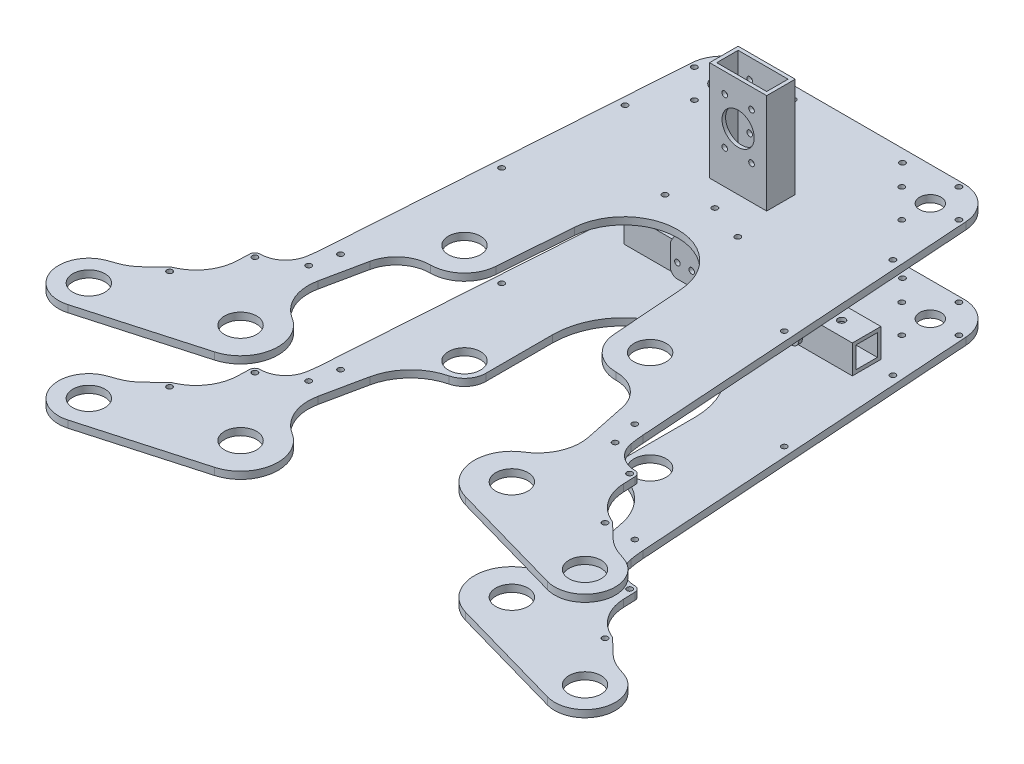
SolidWorks part; units mm, degrees
ref_plane "Alzado" through (0, 0, 0) normal (0, 0, 1) x (1, 0, 0)
ref_plane "Planta" through (0, 0, 0) normal (0, 1, 0) x (1, 0, 0)
ref_plane "Vista lateral" through (0, 0, 0) normal (1, 0, 0) x (0, 0, -1)
sketch "llantas" plane through (0, 0, 0) normal (0, 1, 0) x (1, 0, 0)
  line L0 (0, 221.5734) -> (0, 0) construction
  line L1 (-215.9, 0) -> (0, 0) construction
  circle A0 centre (-93.6625, 101.6) radius 50.8
  circle A1 centre (-215.9, 0) radius 38.1
  circle A2 centre (215.9, 0) radius 38.1
  circle A3 centre (93.6625, 101.6) radius 50.8
  dimension "D1" = 101.6
  dimension "D2" = 42.8625
  dimension "D3" = 177.8
  dimension "D4" = 76.2
  dimension "D5" = 101.6
sketch "cono" plane through (0, 0, 0) normal (1, 0, 0) x (0, 0, -1)
  line L0 (-76.2, 23.114) -> (-22.987, 324.358)
  line L1 (-22.987, 324.358) -> (22.987, 324.358)
  line L2 (0, 324.358) -> (0, 23.114) construction
  line L3 (76.2, 23.114) -> (-76.2, 23.114) construction
  line L4 (-76.2, 23.114) -> (-106.426, 23.114)
  line L5 (-106.426, 23.114) -> (-106.426, 0)
  line L6 (-106.426, 0) -> (106.426, 0)
  line L7 (0, 0) -> (0, 23.114)
  line L8 (-76.2, 23.114) -> (76.2, 23.114)
  line L9 (-80.283, 0) -> (80.283, 0)
  line L10 (221.5734, 0) -> (0, 0) construction
  line L11 (106.426, 23.114) -> (106.426, 0)
  line L12 (76.2, 23.114) -> (106.426, 23.114)
  line L13 (76.2, 23.114) -> (22.987, 324.358)
  line L14 (0, 220.8278) -> (41.275, 220.8278) construction
  dimension "D1" = 324.358
  dimension "D2" = 23.114
  dimension "D3" = 22.987
  dimension "D4" = 152.4
  dimension "D5" = 212.852
  dimension "D6" = 41.275
  dimension "D7" = 220.8278
sketch "Croquis4" plane through (0, 0, 0) normal (0, 1, 0) x (1, 0, 0)
  line L11 (0, 293.4478) -> (0, -300.8756) construction
  circle A36 centre (0, 179.087) radius 32.258
  dimension "D4" = 64.516
ref_plane "Plano1" through (0, 184.15, 0) normal (0, 1, 0) x (1, 0, 0)
sketch "Croquis11" plane through (0, 184.15, 0) normal (0, 1, 0) x (1, 0, 0)
  line L0 (0, -106.426) -> (0, 106.426) construction
  line L1 (-101.7784, 180.6897) -> (-111.1757, -58.1023) construction
  line L2 (0, 0) -> (0, -47.7539) construction
  line L3 (-82.7561, 181.459) -> (-54.1087, -55.7947) construction
  line L4 (-102.0644, -224.6803) -> (-63.9644, -63.6256) construction
  line L5 (-139.2356, -215.8869) -> (-101.1356, -54.8321) construction
  line L6 (0, 0) -> (-82.55, -59.2289) construction
  line L7 (0, 0) -> (0, -106.426) construction
  line L14 (-126.947, -202.253) -> (-226.9506, -237.178) construction
  line L15 (-114.353, -238.3143) -> (-214.3566, -273.2393) construction
  line L16 (0, 293.4478) -> (0, -300.8756) construction
  line L17 (-220.6536, -283.7836) -> (-120.65, -283.7836) construction
  circle A0 centre (0, 0) radius 47.7539 construction
  circle A1 centre (-82.55, -59.2289) radius 50.8
  circle A2 centre (-92.2365, 180.3142) radius 30
  arc A3 (-82.7561, 181.459) -> (-101.7784, 180.6897) centre (-92.2365, 180.3142) ccw construction
  arc A4 (-111.1757, -58.1023) -> (-54.1087, -55.7947) centre (-82.55, -59.2289) ccw construction
  arc A6 (-139.2356, -215.8869) -> (-102.0644, -224.6803) centre (-120.65, -220.2836) ccw construction
  arc A7 (-63.9644, -63.6256) -> (-101.1356, -54.8321) centre (-82.55, -59.2289) ccw construction
  circle A12 centre (-120.65, -220.2836) radius 50.8
  circle A13 centre (-220.6536, -255.2086) radius 28.575
  arc A14 (-226.9506, -237.178) -> (-214.3566, -273.2393) centre (-220.6536, -255.2086) ccw construction
  arc A15 (-114.353, -238.3143) -> (-139.2356, -215.8869) centre (-120.65, -220.2836) ccw construction
  dimension "D1" = 101.6
  dimension "D4" = 60
  dimension "D5" = 19.0986
  dimension "D6" = 57.2958
  dimension "D10" = 38.1972
  dimension "D17" = 101.6
  dimension "D13" = 57.15
  dimension "D14" = 38.1972
  dimension "D2" = 101.6
  dimension "D3" = 165.1
  dimension "D8" = 69.85
  dimension "D9" = 12.7
  dimension "D12" = 239.5431
sketch "Croquis40" plane through (0, 184.15, 0) normal (0, 1, 0) x (1, 0, 0)
  line L0 (-117.475, -110.0289) -> (117.475, -110.0289) construction
  line L1 (-117.475, -110.0289) -> (-117.475, -344.9789) construction
  line L2 (117.475, -110.0289) -> (117.475, -344.9789) construction
  line L3 (-117.475, -344.9789) -> (117.475, -344.9789) construction
  line L4 (0, 0) -> (0, -110.0289)
  circle A1 centre (-82.55, -59.2289) radius 50.8 construction
  dimension "D1" = 234.95
ref_plane "Plano2" through (0, 95.25, 0) normal (0, 1, 0) x (1, 0, 0)
sketch "Croquis12" plane through (0, 95.25, 0) normal (0, 1, 0) x (1, 0, 0)
  line L0 (0, 0) -> (0, -63.4576) construction
  circle A0 centre (0, 0) radius 63.4576 construction
  circle A1 centre (-82.55, -59.2289) radius 50.8
  circle A2 centre (-82.55, -59.2289) radius 50.8 construction
sketch "Croquis42" plane through (0, 184.15, 0) normal (0, 1, 0) x (1, 0, 0)
  line L10 (142.9479, -125.9298) -> (122.1686, 182.3319)
  line L11 (-47.6217, 3.5515) -> (-52.471, -61.4721)
  line L12 (-112.3836, -113.6275) -> (-120.3575, -151.7275)
  line L13 (-120.65, -220.2836) -> (-220.6536, -255.2086) construction
  line L14 (-111.5648, -252.3593) -> (-213.299, -281.1746)
  line L15 (0, 226.6032) -> (0, -226.6032) construction
  line L17 (229.5516, -229.7302) -> (219.3033, -226.1511)
  line L18 (-229.5516, -229.7302) -> (-219.3033, -226.1511)
  line L19 (-142.9479, -125.9298) -> (-122.1686, 182.3319)
  line L20 (-126.947, -202.253) -> (-226.9506, -237.178) construction
  line L21 (-92.2365, 210.3142) -> (92.2365, 210.3142)
  line L22 (111.5648, -252.3593) -> (213.299, -281.1746)
  line L23 (112.3836, -113.6275) -> (120.3575, -151.7275)
  line L24 (47.6217, 3.5515) -> (52.471, -61.4721)
  circle A11 centre (-220.6536, -255.2086) radius 14.2875
  circle A17 centre (-120.65, -220.2836) radius 14.2875
  circle A18 centre (-82.55, -59.2289) radius 14.2875
  arc A20 (47.6217, 3.5515) -> (-47.6217, 3.5515) centre (0, 0) ccw
  circle A21 centre (92.2365, 180.3142) radius 25.4 construction
  circle A22 centre (0, 0) radius 47.7539 construction
  arc A23 (-82.55, -89.3914) -> (-52.471, -61.4721) centre (-82.55, -59.2289) ccw
  arc A24 (-82.55, -89.3914) -> (-112.3836, -113.6275) centre (-82.55, -119.8714) ccw
  arc A25 (-111.5648, -252.3593) -> (-103.1106, -191.933) centre (-120.65, -220.2836) ccw
  arc A26 (-120.3575, -151.7275) -> (-103.1106, -191.933) centre (-83.0655, -159.5323) ccw
  arc A28 (-229.5516, -229.7302) -> (-213.299, -281.1746) centre (-220.6536, -255.2086) ccw
  circle A29 centre (120.65, -220.2836) radius 33.3375 construction
  circle A30 centre (117.6365, 180.3142) radius 2.4892
  circle A31 centre (-92.2365, 180.3142) radius 30 construction
  arc A32 (-92.2365, 210.3142) -> (-122.1686, 182.3319) centre (-92.2365, 180.3142) ccw
  circle A33 centre (-120.65, -220.2836) radius 33.3375 construction
  circle A34 centre (-92.2365, 180.3142) radius 25.4 construction
  circle A35 centre (-92.2365, 205.7142) radius 2.4892
  circle A36 centre (-66.8365, 180.3142) radius 2.4892
  circle A37 centre (-92.2365, 154.9142) radius 2.4892
  circle A38 centre (-117.6365, 180.3142) radius 2.4892
  circle A39 centre (92.2365, 154.9142) radius 2.4892
  circle A40 centre (66.8365, 180.3142) radius 2.4892
  circle A41 centre (92.2365, 205.7142) radius 2.4892
  arc A42 (92.2365, 210.3142) -> (122.1686, 182.3319) centre (92.2365, 180.3142) cw
  arc A43 (229.5516, -229.7302) -> (213.299, -281.1746) centre (220.6536, -255.2086) cw
  arc A44 (120.3575, -151.7275) -> (103.1106, -191.933) centre (83.0655, -159.5323) cw
  arc A45 (111.5648, -252.3593) -> (103.1106, -191.933) centre (120.65, -220.2836) cw
  arc A46 (82.55, -89.3914) -> (112.3836, -113.6275) centre (82.55, -119.8714) cw
  arc A47 (82.55, -89.3914) -> (52.471, -61.4721) centre (82.55, -59.2289) cw
  circle A48 centre (82.55, -59.2289) radius 14.2875
  circle A49 centre (120.65, -220.2836) radius 14.2875
  circle A50 centre (220.6536, -255.2086) radius 14.2875
  arc A52 (142.9479, -125.9298) -> (219.3033, -226.1511) centre (256.9891, -118.2425) ccw
  arc A53 (-219.3033, -226.1511) -> (-142.9479, -125.9298) centre (-256.9891, -118.2425) ccw
  circle A54 centre (-92.2365, 180.3142) radius 9.5631
  circle A55 centre (92.2365, 180.3142) radius 9.5631
  point P18 (-170.6518, -237.7461)
  point P52 (-92.2365, 180.3142)
  point P66 (148.0256, -201.2583)
  point P83 (0, 210.3142)
  point P85 (92.2365, 180.3142)
  point P86 (170.6518, -237.7461)
  point P90 (-148.0256, -201.2583)
  dimension "D1" = 28.575
  dimension "D2" = 19.05
  dimension "D3" = 12.7
  dimension "D4" = 15.875
  dimension "D5" = 38.1
  dimension "D7" = 30.48
  dimension "D8" = 50.8
  dimension "D9" = 4.9784
  dimension "D11" = 114.3
  dimension "D12" = 19.1262
  dimension "D6" = 38.1
  dimension "D10" = 4
extrude "4400-23-P-0501" add sketch "Croquis42" along normal blind 6.35
sketch "Croquis44" plane through (0, 95.25, 0) normal (0, 1, 0) x (1, 0, 0)
  line L0 (92.2365, 210.3142) -> (-92.2365, 210.3142) construction
  line L1 (-122.1686, 182.3319) -> (-142.9479, -125.9298) construction
  line L2 (92.2365, 210.3142) -> (-92.2365, 210.3142)
  line L3 (-122.1686, 182.3319) -> (-142.9479, -125.9298)
  line L4 (142.9479, -125.9298) -> (122.1686, 182.3319) construction
  line L5 (229.5516, -229.7302) -> (219.3033, -226.1511) construction
  line L6 (111.5648, -252.3593) -> (213.299, -281.1746) construction
  line L7 (112.3836, -113.6275) -> (120.3575, -151.7275) construction
  line L10 (-120.3575, -151.7275) -> (-112.3836, -113.6275) construction
  line L11 (-213.299, -281.1746) -> (-111.5648, -252.3593) construction
  line L12 (-219.3033, -226.1511) -> (-229.5516, -229.7302) construction
  line L13 (142.9479, -125.9298) -> (122.1686, 182.3319)
  line L14 (229.5516, -229.7302) -> (219.3033, -226.1511)
  line L15 (111.5648, -252.3593) -> (213.299, -281.1746)
  line L16 (112.3836, -113.6275) -> (120.3575, -151.7275)
  line L19 (-120.3575, -151.7275) -> (-112.3836, -113.6275)
  line L20 (-213.299, -281.1746) -> (-111.5648, -252.3593)
  line L21 (-219.3033, -226.1511) -> (-229.5516, -229.7302)
  line L22 (-63.4576, -59.2289) -> (-63.4576, 0)
  line L23 (63.4576, -59.2289) -> (63.4576, 0)
  line L24 (0, 0) -> (0, -147.841) construction
  arc A0 (-219.3033, -226.1511) -> (-142.9479, -125.9298) centre (-256.9891, -118.2425) ccw construction
  arc A1 (-92.2365, 210.3142) -> (-122.1686, 182.3319) centre (-92.2365, 180.3142) ccw construction
  arc A2 (-219.3033, -226.1511) -> (-142.9479, -125.9298) centre (-256.9891, -118.2425) ccw
  arc A3 (-92.2365, 210.3142) -> (-122.1686, 182.3319) centre (-92.2365, 180.3142) ccw
  arc A4 (122.1686, 182.3319) -> (92.2365, 210.3142) centre (92.2365, 180.3142) ccw construction
  arc A5 (142.9479, -125.9298) -> (219.3033, -226.1511) centre (256.9891, -118.2425) ccw construction
  arc A6 (213.299, -281.1746) -> (229.5516, -229.7302) centre (220.6536, -255.2086) ccw construction
  arc A7 (103.1106, -191.933) -> (111.5648, -252.3593) centre (120.65, -220.2836) ccw construction
  arc A8 (103.1106, -191.933) -> (120.3575, -151.7275) centre (83.0655, -159.5323) ccw construction
  arc A14 (-120.3575, -151.7275) -> (-103.1106, -191.933) centre (-83.0655, -159.5323) ccw construction
  arc A15 (-111.5648, -252.3593) -> (-103.1106, -191.933) centre (-120.65, -220.2836) ccw construction
  arc A16 (-229.5516, -229.7302) -> (-213.299, -281.1746) centre (-220.6536, -255.2086) ccw construction
  arc A17 (122.1686, 182.3319) -> (92.2365, 210.3142) centre (92.2365, 180.3142) ccw
  arc A18 (142.9479, -125.9298) -> (219.3033, -226.1511) centre (256.9891, -118.2425) ccw
  arc A19 (213.299, -281.1746) -> (229.5516, -229.7302) centre (220.6536, -255.2086) ccw
  arc A20 (103.1106, -191.933) -> (111.5648, -252.3593) centre (120.65, -220.2836) ccw
  arc A21 (103.1106, -191.933) -> (120.3575, -151.7275) centre (83.0655, -159.5323) ccw
  arc A27 (-120.3575, -151.7275) -> (-103.1106, -191.933) centre (-83.0655, -159.5323) ccw
  arc A28 (-111.5648, -252.3593) -> (-103.1106, -191.933) centre (-120.65, -220.2836) ccw
  arc A29 (-229.5516, -229.7302) -> (-213.299, -281.1746) centre (-220.6536, -255.2086) ccw
  circle A30 centre (92.2365, 180.3142) radius 9.5631 construction
  circle A31 centre (92.2365, 154.9142) radius 2.4892 construction
  circle A32 centre (117.6365, 180.3142) radius 2.4892 construction
  circle A33 centre (92.2365, 205.7142) radius 2.4892 construction
  circle A34 centre (66.8365, 180.3142) radius 2.4892 construction
  circle A35 centre (-92.2365, 180.3142) radius 9.5631 construction
  circle A36 centre (-66.8365, 180.3142) radius 2.4892 construction
  circle A37 centre (-92.2365, 205.7142) radius 2.4892 construction
  circle A38 centre (-117.6365, 180.3142) radius 2.4892 construction
  circle A39 centre (-92.2365, 154.9142) radius 2.4892 construction
  circle A40 centre (220.6536, -255.2086) radius 14.2875 construction
  circle A41 centre (120.65, -220.2836) radius 14.2875 construction
  circle A42 centre (82.55, -59.2289) radius 14.2875 construction
  circle A43 centre (-82.55, -59.2289) radius 14.2875 construction
  circle A44 centre (-120.65, -220.2836) radius 14.2875 construction
  circle A45 centre (-220.6536, -255.2086) radius 14.2875 construction
  circle A46 centre (92.2365, 180.3142) radius 9.5631
  circle A47 centre (92.2365, 154.9142) radius 2.4892
  circle A48 centre (117.6365, 180.3142) radius 2.4892
  circle A49 centre (92.2365, 205.7142) radius 2.4892
  circle A50 centre (66.8365, 180.3142) radius 2.4892
  circle A51 centre (-92.2365, 180.3142) radius 9.5631
  circle A52 centre (-66.8365, 180.3142) radius 2.4892
  circle A53 centre (-92.2365, 205.7142) radius 2.4892
  circle A54 centre (-117.6365, 180.3142) radius 2.4892
  circle A55 centre (-92.2365, 154.9142) radius 2.4892
  circle A56 centre (220.6536, -255.2086) radius 14.2875
  circle A57 centre (120.65, -220.2836) radius 14.2875
  circle A58 centre (82.55, -59.2289) radius 14.2875
  circle A59 centre (-82.55, -59.2289) radius 14.2875
  circle A60 centre (-120.65, -220.2836) radius 14.2875
  circle A61 centre (-220.6536, -255.2086) radius 14.2875
  arc A62 (63.4576, 0) -> (-63.4576, 0) centre (0, 0) ccw
  arc A64 (-63.4576, -59.2289) -> (-77.9, -77.7463) centre (-82.55, -59.2289) cw
  arc A65 (-112.3836, -113.6275) -> (-77.9, -77.7463) centre (-66.477, -123.2353) cw
  circle A66 centre (0, 0) radius 63.4576 construction
  arc A67 (112.3836, -113.6275) -> (77.9, -77.7463) centre (66.477, -123.2353) ccw
  arc A68 (63.4576, -59.2289) -> (77.9, -77.7463) centre (82.55, -59.2289) ccw
extrude "4400-23-P-0502" add sketch "Croquis44" along normal blind 6.35
sketch "Croquis45" plane through (0, 95.25, 0) normal (0, -1, 0) x (1, 0, 0)
  line L7 (-126.947, 202.253) -> (-226.9506, 237.178) construction
  circle A0 centre (-189.6273, 213.7178) radius 4.7625 construction
  circle A1 centre (-189.6273, 213.7178) radius 2.4892
  circle A6 centre (-220.6536, 255.2086) radius 38.1
  circle A7 centre (-220.6536, 255.2086) radius 38.1 construction
  circle A9 centre (-120.65, 220.2836) radius 63.5
  circle A10 centre (-120.65, 220.2836) radius 63.5 construction
  dimension "D1" = 9.525
  dimension "D2" = 4.9784
  dimension "D5" = 5.08
  dimension "D3" = 9.525
  dimension "D4" = 12.7
sketch "Croquis46" plane through (0, 190.5, 0) normal (0, 1, 0) x (1, 0, 0)
  line L0 (-184.6841, -242.6467) -> (-180.5992, -241.2201) construction
  line L1 (-126.947, -202.253) -> (-226.9506, -237.178) construction
  line L2 (-220.6536, -255.2086) -> (-120.65, -220.2836) construction
  line L3 (-182.6417, -241.9334) -> (-193.6494, -210.4142) construction
  line L4 (-166.6601, -156.7836) -> (-120.65, -156.7836) construction
  line L5 (-215.2247, -224.639) -> (-196.9587, -206.9893)
  line L6 (-172.6356, -195.3721) -> (-195.6603, -206.0971)
  line L7 (-172.6356, -195.3721) -> (-171.4196, -161.3759)
  line L8 (0, 0) -> (0, -195.4432) construction
  line L9 (166.6601, -156.7836) -> (120.65, -156.7836) construction
  line L10 (182.6417, -241.9334) -> (193.6494, -210.4142) construction
  line L11 (220.6536, -255.2086) -> (120.65, -220.2836) construction
  line L12 (184.6841, -242.6467) -> (180.5992, -241.2201) construction
  line L13 (172.6356, -195.3721) -> (171.4196, -161.3759)
  line L14 (172.6356, -195.3721) -> (195.6603, -206.0971)
  line L15 (215.2247, -224.639) -> (196.9587, -206.9893)
  circle A0 centre (-220.6536, -255.2086) radius 38.1 construction
  circle A1 centre (-193.6494, -210.4142) radius 4.7625 construction
  circle A2 centre (-193.6494, -210.4142) radius 2.4892
  circle A3 centre (-166.6601, -161.5461) radius 4.7625 construction
  circle A4 centre (-166.6601, -161.5461) radius 2.4892
  arc A5 (-219.3033, -226.1511) -> (-142.9479, -125.9298) centre (-256.9891, -118.2425) ccw construction
  circle A6 centre (-120.65, -220.2836) radius 63.5 construction
  arc A7 (-196.9587, -206.9893) -> (-195.6603, -206.0971) centre (-193.6494, -210.4142) cw
  arc A8 (-171.4196, -161.3759) -> (-166.6601, -156.7836) centre (-166.6601, -161.5461) cw
  arc A9 (-166.6601, -156.7836) -> (-144.4349, -138.1433) centre (-166.6601, -134.2137) ccw
  arc A10 (-215.2247, -224.639) -> (-144.4349, -138.1433) centre (-256.9891, -118.2425) ccw
  circle A11 centre (166.6601, -161.5461) radius 4.7625 construction
  circle A12 centre (193.6494, -210.4142) radius 4.7625 construction
  arc A13 (215.2247, -224.639) -> (144.4349, -138.1433) centre (256.9891, -118.2425) cw
  arc A14 (166.6601, -156.7836) -> (144.4349, -138.1433) centre (166.6601, -134.2137) cw
  arc A15 (171.4196, -161.3759) -> (166.6601, -156.7836) centre (166.6601, -161.5461) ccw
  arc A16 (196.9587, -206.9893) -> (195.6603, -206.0971) centre (193.6494, -210.4142) ccw
  circle A17 centre (166.6601, -161.5461) radius 2.4892
  circle A18 centre (193.6494, -210.4142) radius 2.4892
  point P20 (-182.6417, -241.9334)
  arc M29 (219.3033, -226.1511) -> (142.9479, -125.9298) centre (256.9891, -118.2425) cw
  arc M35 (-142.9479, -125.9298) -> (-219.3033, -226.1511) centre (-256.9891, -118.2425) cw
  dimension "D1" = 4.9784
  dimension "D2" = 9.525
  dimension "D4" = 6.35
  dimension "D3" = 9.525
  dimension "D5" = 25.4
extrude "Saliente-Extruir2" add sketch "Croquis46" against normal up to surface (6.35 mm away) contours A9 A8 L7 A4 M35 | A7 L5 A2 L6 M35 | L13 A15 A14 A17 M29 | A18 L15 A16 L14 M29 region at (-162.2772, 190.5, 168.9624) region at (-205.7326, 190.5, 216.1858) region at (162.2772, 190.5, 168.9624) region at (183.9298, 190.5, 201.203) up to face at (0, 184.15, 101.9028)
fillet "Redondeo1" radius 38.1 2 edges at (-215.2247, 187.325, 224.639) (-172.6356, 187.325, 195.3721)
extrude "Saliente-Extruir3" add sketch "Croquis46<3>" against normal up to surface (95.25 mm away) from surface contours A9 A8 L7 A4 M35 | A7 L5 A2 L6 M35 | L13 A15 A14 A17 M29 | A18 L15 A16 L14 M29 region at (-162.2772, 190.5, 168.9624) region at (-205.7326, 190.5, 216.1858) region at (162.2772, 190.5, 168.9624) region at (183.9298, 190.5, 201.203) up to face at (0, 95.25, 100.1304) starting at face at (-120.65, 101.6, 234.5711)
sketch "Croquis46<3>" plane through (0, 190.5, 0) normal (0, 1, 0) x (1, 0, 0) same geometry as "Croquis46"
fillet "Redondeo2" radius 38.1 2 edges at (-215.2247, 98.425, 224.639) (-172.6356, 98.425, 195.3721)
fillet "Redondeo3" radius 38.1 2 edges at (215.2247, 187.325, 224.639) (172.6356, 187.325, 195.3721)
fillet "Redondeo4" radius 38.1 2 edges at (215.2247, 98.425, 224.639) (172.6356, 98.425, 195.3721)
sketch "Croquis47" plane through (0, 190.5, 0) normal (0, 1, 0) x (1, 0, 0)
  line L0 (-139.2356, -215.8869) -> (-101.1356, -54.8321) construction
  line L4 (0, 0) -> (0, -211.1114) construction
  line L9 (-101.7784, 180.6897) -> (-111.1757, -58.1023) construction
  line L12 (92.2365, 210.3142) -> (-92.2365, 210.3142) construction
  line L14 (-82.7561, 181.459) -> (-54.1087, -55.7947) construction
  circle A0 centre (-136.2788, -144.0836) radius 4.7625 construction
  circle A1 centre (-136.2788, -144.0836) radius 2.4892
  circle A2 centre (-130.8514, -121.1414) radius 4.7625 construction
  circle A3 centre (-130.8514, -121.1414) radius 2.4892
  circle A5 centre (-120.65, -220.2836) radius 63.5 construction
  circle A7 centre (-82.55, -59.2289) radius 50.8 construction
  circle A8 centre (130.8514, -121.1414) radius 2.4892
  circle A9 centre (130.8514, -121.1414) radius 4.7625 construction
  circle A10 centre (136.2788, -144.0836) radius 2.4892
  circle A11 centre (136.2788, -144.0836) radius 4.7625 construction
  circle A12 centre (-119.0948, 120.1517) radius 2.4892
  circle A13 centre (-119.0948, 120.1517) radius 4.7625 construction
  circle A14 centre (-125.6973, 16.9711) radius 2.4892
  circle A15 centre (-125.6973, 16.9711) radius 4.7625 construction
  circle A17 centre (-92.2365, 180.3142) radius 30 construction
  circle A18 centre (125.6973, 16.9711) radius 4.7625 construction
  circle A19 centre (125.6973, 16.9711) radius 2.4892
  circle A20 centre (119.0948, 120.1517) radius 4.7625 construction
  circle A21 centre (119.0948, 120.1517) radius 2.4892
  circle A22 centre (-48.584, 199.2017) radius 4.7625 construction
  circle A23 centre (-48.584, 199.2017) radius 2.4892
  circle A24 centre (48.584, 199.2017) radius 2.4892
  circle A25 centre (48.584, 199.2017) radius 4.7625 construction
  circle A26 centre (0, 80.9201) radius 4.7625 construction
  circle A27 centre (0, 80.9201) radius 2.4892
  circle A28 centre (-32.3905, 68.9263) radius 2.4892
  circle A29 centre (-32.3905, 68.9263) radius 4.7625 construction
  circle A31 centre (0, 0) radius 63.4576 construction
  circle A32 centre (32.3905, 68.9263) radius 2.4892
  circle A33 centre (32.3905, 68.9263) radius 4.7625 construction
  dimension "D1" = 4.9784
  dimension "D2" = 9.525
  dimension "D3" = 8.89
  dimension "D4" = 8.89
  dimension "D5" = 12.7
  dimension "D6" = 6.35
  dimension "D7" = 9.525
  dimension "D8" = 4.9784
  dimension "D9" = 12.7
  dimension "D10" = 10.16
  dimension "D11" = 25.4
  dimension "D12" = 25.4
  dimension "D13" = 4.9784
  dimension "D14" = 9.525
  dimension "D15" = 8.89
  dimension "D16" = 6.35
  dimension "D17" = 9.525
  dimension "D18" = 4.9784
  dimension "D19" = 12.7
  dimension "D20" = 65.3447
  dimension "D21" = 12.7
  dimension "D22" = 31.75
extrude "Cortar-Extruir1" cut sketch "Croquis47" against normal through all
sketch "Croquis48" plane through (0, 101.6, 0) normal (0, 1, 0) x (1, 0, 0)
  line L1 (-101.6, 127) -> (101.6, 127)
  line L2 (-101.6, 127) -> (-101.6, 101.6)
  line L3 (-101.6, 101.6) -> (101.6, 101.6)
  line L4 (101.6, 127) -> (101.6, 101.6)
  line L5 (-101.6, 127) -> (101.6, 101.6) construction
  line L6 (-101.6, 101.6) -> (101.6, 127) construction
  point P0 (0, 114.3)
  point P5 (0, 0)
  dimension "D1" = 25.4
  dimension "D2" = 203.2
  dimension "D3" = 114.3
extrude "Saliente-Extruir4" add sketch "Croquis48" along normal blind 25.4 from surface separate body starting at face at (-136.2788, 101.6, 146.5728)
shell "Vaciado1" thickness 3.175 removed face at (-101.6, 114.3, -114.3) removed face at (101.6, 114.3, -114.3)
sketch "Croquis49" plane through (0, 127, 0) normal (0, 1, 0) x (1, 0, 0)
  line L0 (0, 127) -> (0, 101.6) construction
  line L1 (-101.6, 127) -> (101.6, 127) construction
  line L2 (101.6, 101.6) -> (-101.6, 101.6) construction
  line L3 (-101.6, 114.3) -> (0, 114.3) construction
  line L4 (-101.6, 101.6) -> (-101.6, 127) construction
  line L6 (-25.4, 101.6) -> (25.4, 101.6)
  line L7 (-25.4, 101.6) -> (-25.4, 127)
  line L8 (-25.4, 127) -> (25.4, 127)
  line L9 (25.4, 101.6) -> (25.4, 127)
  line L10 (-25.4, 101.6) -> (25.4, 127) construction
  line L11 (-25.4, 127) -> (25.4, 101.6) construction
  dimension "D1" = 50.8
extrude "Saliente-Extruir5" add sketch "Croquis49" along normal blind 152.4 separate body
shell "Vaciado2" thickness 3.175 removed face at (0, 279.4, -114.3) removed face at (0, 127, -114.3)
sketch "Croquis50" plane through (0, 0, -101.6) normal (0, 0, 1) x (1, 0, 0)
  line L0 (-47.6217, 184.15) -> (47.6217, 184.15) construction
  line L1 (0, 241.2619) -> (11.9062, 261.8841) construction
  line L2 (-25.4, 279.4) -> (25.4, 279.4) construction
  line L3 (0, 241.2619) -> (0, 279.4) construction
  circle A0 centre (0, 241.2619) radius 14.3129
  circle A1 centre (0, 241.2619) radius 23.8125 construction
  circle A2 centre (11.9062, 261.8841) radius 2.4892
  circle A3 centre (23.8125, 241.2619) radius 2.4892 construction
  circle A4 centre (11.9062, 220.6397) radius 2.4892
  circle A5 centre (-11.9063, 220.6397) radius 2.4892
  circle A6 centre (-23.8125, 241.2619) radius 2.4892 construction
  circle A7 centre (-11.9063, 261.8841) radius 2.4892
  point P10 (0, 0)
  point P11 (0, 0)
  point P23 (3.5514, 264.8081)
  point P24 (-20.5026, 253.373)
  point P25 (-11.7836, 261.9544)
  point P26 (0, 0)
  dimension "D1" = 57.1119
  dimension "D2" = 28.6258
  dimension "D3" = 47.625
  dimension "D4" = 4.9784
  dimension "D6" = 23.8125
  dimension "D5" = 6
extrude "Cortar-Extruir2" cut sketch "Croquis50" against normal through all
sketch "Croquis53" plane through (0, 0, -101.6) normal (0, 0, 1) x (1, 0, 0)
  line L0 (-101.6, 114.3) -> (101.6, 114.3) construction
  line L1 (-101.6, 127) -> (-101.6, 101.6) construction
  line L2 (101.6, 127) -> (101.6, 101.6) construction
  line L3 (0, 114.3) -> (12.7, 114.3) construction
  line L4 (0, 114.3) -> (0, 279.4) construction
  line L5 (-25.4, 279.4) -> (25.4, 279.4) construction
  line L6 (-12.7, 114.3) -> (-12.7, 127) construction
  line L7 (50.8, 101.6) -> (-50.8, 101.6)
  line L9 (101.6, 101.6) -> (-101.6, 101.6) construction
  line L10 (-57.15, 107.95) -> (-57.15, 125.3481)
  line L11 (101.6, 127) -> (-101.6, 127) construction
  line L12 (-56.3451, 128.4425) -> (-27.2168, 180.6403)
  line L13 (-25.4, 279.4) -> (-25.4, 127) construction
  line L14 (-21.6717, 183.896) -> (21.6717, 183.896)
  line L15 (57.15, 107.95) -> (57.15, 125.3481)
  line L16 (56.3451, 128.4425) -> (27.2168, 180.6403)
  circle A0 centre (0, 114.3) radius 2.4892
  circle A1 centre (12.7, 114.3) radius 2.4892
  circle A2 centre (25.4, 114.3) radius 2.4892
  circle A3 centre (38.1, 114.3) radius 2.4892
  circle A4 centre (50.8, 114.3) radius 2.4892
  circle A5 centre (-50.8, 114.3) radius 2.4892
  circle A6 centre (-38.1, 114.3) radius 2.4892
  circle A7 centre (-25.4, 114.3) radius 2.4892
  circle A8 centre (-12.7, 114.3) radius 2.4892
  circle A10 centre (-12.7, 127) radius 2.4892 [skipped]
  circle A11 centre (12.7, 127) radius 2.4892 [skipped]
  circle A12 centre (-12.7, 139.7) radius 2.4892
  circle A13 centre (12.7, 139.7) radius 2.4892
  circle A14 centre (-12.7, 152.4) radius 2.4892
  circle A15 centre (12.7, 152.4) radius 2.4892
  circle A16 centre (-12.7, 165.1) radius 2.4892
  circle A17 centre (12.7, 165.1) radius 2.4892
  circle A18 centre (-12.7, 177.8) radius 2.4892
  circle A19 centre (12.7, 177.8) radius 2.4892
  arc A20 (57.15, 107.95) -> (50.8, 101.6) centre (50.8, 107.95) cw
  arc A21 (57.15, 125.3481) -> (56.3451, 128.4425) centre (50.8, 125.3481) ccw
  arc A22 (27.2168, 180.6403) -> (21.6717, 183.896) centre (21.6717, 177.546) ccw
  arc A23 (-27.2168, 180.6403) -> (-21.6717, 183.896) centre (-21.6717, 177.546) cw
  arc A24 (-57.15, 125.3481) -> (-56.3451, 128.4425) centre (-50.8, 125.3481) cw
  arc A25 (-50.8, 101.6) -> (-57.15, 107.95) centre (-50.8, 107.95) cw
  point P62 (0, 0)
  point P63 (0, 101.6)
  point P65 (0, 183.896)
  point P68 (57.15, 101.6)
  point P71 (57.15, 127)
  point P74 (25.4, 183.896)
  point P77 (-25.4, 183.896)
  point P80 (-57.15, 127)
  point P83 (-57.15, 101.6)
  dimension "D1" = 4.9784
  dimension "D4" = 6
  dimension "D8" = 6.35
  dimension "D3" = 12.7
  dimension "D5" = 12.7
  dimension "D6" = 6.096
  dimension "D7" = 6.35
  dimension "D2" = 5
extrude "Saliente-Extruir6" add sketch "Croquis53" along normal blind 3.175 separate body
sketch "Croquis55" plane through (0, 0, -98.425) normal (0, 0, 1) x (1, 0, 0)
  circle A0 centre (-12.7, 114.3) radius 2.4892 construction
  circle A1 centre (-12.7, 139.7) radius 2.4892 construction
  circle A2 centre (-25.4, 114.3) radius 2.4892 construction
  circle A3 centre (-38.1, 114.3) radius 2.4892 construction
  circle A4 centre (-50.8, 114.3) radius 2.4892 construction
  circle A5 centre (-12.7, 114.3) radius 2.4892
  circle A6 centre (-12.7, 139.7) radius 2.4892
  circle A7 centre (-25.4, 114.3) radius 2.4892
  circle A8 centre (-38.1, 114.3) radius 2.4892
  circle A9 centre (-50.8, 114.3) radius 2.4892
  circle A10 centre (-12.7, 165.1) radius 2.4892 construction
  circle A11 centre (-12.7, 152.4) radius 2.4892 construction
  circle A12 centre (-12.7, 165.1) radius 2.4892
  circle A13 centre (-12.7, 152.4) radius 2.4892
  circle A14 centre (-12.7, 177.8) radius 2.4892 construction
  circle A15 centre (-12.7, 177.8) radius 2.4892
  circle A16 centre (12.7, 165.1) radius 2.4892 construction
  circle A17 centre (12.7, 177.8) radius 2.4892 construction
  circle A18 centre (12.7, 165.1) radius 2.4892
  circle A19 centre (12.7, 177.8) radius 2.4892
  circle A20 centre (0, 114.3) radius 2.4892 construction
  circle A21 centre (12.7, 114.3) radius 2.4892 construction
  circle A22 centre (12.7, 139.7) radius 2.4892 construction
  circle A23 centre (12.7, 152.4) radius 2.4892 construction
  circle A24 centre (0, 114.3) radius 2.4892
  circle A25 centre (12.7, 114.3) radius 2.4892
  circle A26 centre (12.7, 139.7) radius 2.4892
  circle A27 centre (12.7, 152.4) radius 2.4892
  circle A28 centre (50.8, 114.3) radius 2.4892 construction
  circle A29 centre (38.1, 114.3) radius 2.4892 construction
  circle A30 centre (25.4, 114.3) radius 2.4892 construction
  circle A31 centre (50.8, 114.3) radius 2.4892
  circle A32 centre (38.1, 114.3) radius 2.4892
  circle A33 centre (25.4, 114.3) radius 2.4892
extrude "Cortar-Extruir3" cut sketch "Croquis55" against normal up to surface (28.575 mm away) up to face at (-9.417, 261.8841, -127)
sketch "Croquis56" plane through (0, 101.6, 0) normal (0, -1, 0) x (1, 0, 0)
  line L0 (0, -101.6) -> (0, -127) construction
  line L1 (101.6, -101.6) -> (-101.6, -101.6) construction
  line L2 (-101.6, -127) -> (101.6, -127) construction
  line L3 (0, -114.3) -> (-101.6, -114.3) construction
  line L4 (-101.6, -101.6) -> (-101.6, -127) construction
  line L5 (-25.4, -114.3) -> (-25.4, -127) construction
  circle A0 centre (-47.625, -114.3) radius 3.2639
  circle A1 centre (-79.375, -114.3) radius 3.2639
  circle A2 centre (79.375, -114.3) radius 3.2639
  circle A3 centre (47.625, -114.3) radius 3.2639
  dimension "D1" = 25.4
  dimension "D2" = 6.5278
  dimension "D3" = 31.75
  dimension "D4" = 22.225
extrude "Cortar-Extruir4" cut sketch "Croquis56" against normal up to surface (25.4 mm away) up to face at (0, 127, -114.3)
equation "\"D5@Croquis11\"=12*5MM/PI"
equation "\"D6@Croquis11\"=36*5mm/pi"
equation "\"D7@Croquis11\"=(120*5mm)+1mm"
equation "\"D10@Croquis11\"=24*5mm/pi"
equation "\"D11@Croquis11\"=(90*5mm)+1mm"
equation "\"D14@Croquis11\"=24*5mm/pi"
equation "\"D15@Croquis11\"=(70*5mm)+1mm"
